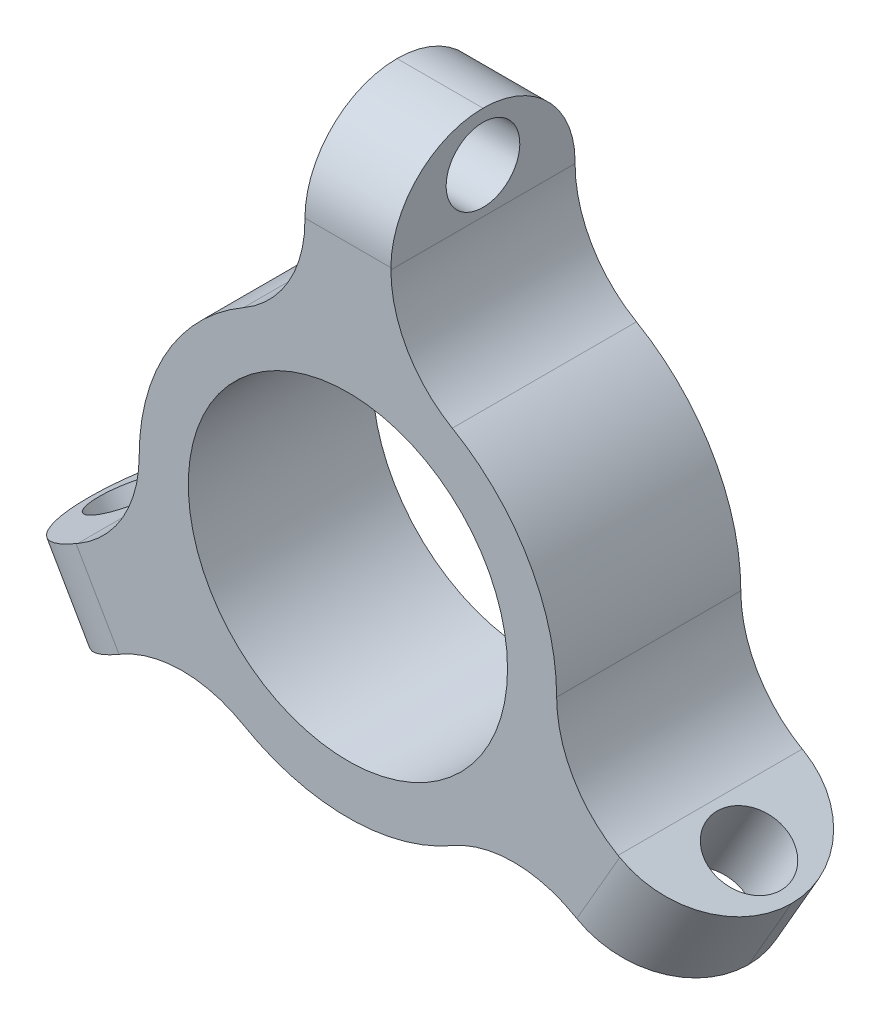
SolidWorks part; units mm, degrees
material "BUTYL"
ref_plane "Plan de face" through (0, 0, 0) normal (0, 0, 1) x (1, 0, 0)
ref_plane "Plan de dessus" through (0, 0, 0) normal (0, 1, 0) x (1, 0, 0)
ref_plane "Plan de droite" through (0, 0, 0) normal (1, 0, 0) x (0, 0, -1)
sketch "Esquisse1" plane through (0, 0, 0) normal (0, 0, 1) x (1, 0, 0)
  line L0 (0, 21.0412) -> (0, 29.5771) construction
  line L1 (-3.5, 23.3827) -> (-3.5, 31.0412)
  line L2 (-3.5, 31.0412) -> (3.5, 31.0412)
  line L3 (3.5, 31.0412) -> (3.5, 23.3827)
  line L4 (25.1325, -18.5517) -> (18.5, -14.7224)
  line L5 (28.6325, -12.4895) -> (25.1325, -18.5517)
  line L6 (22, -8.6603) -> (28.6325, -12.4895)
  line L7 (-28.6325, -12.4895) -> (-22, -8.6603)
  line L8 (-25.1325, -18.5517) -> (-28.6325, -12.4895)
  line L9 (-18.5, -14.7224) -> (-25.1325, -18.5517)
  circle A0 centre (0, 0) radius 13
  arc A1 (-8.5, 14.7224) -> (-17, 0) centre (0, 0) ccw
  arc A2 (17, 0) -> (8.5, 14.7224) centre (0, 0) ccw
  arc A3 (-8.5, -14.7224) -> (8.5, -14.7224) centre (0, 0) ccw
  arc A4 (-8.5, -14.7224) -> (-18.5, -14.7224) centre (-13.5, -23.3827) ccw
  arc A5 (-8.5, 14.7224) -> (-3.5, 23.3827) centre (-13.5, 23.3827) ccw
  arc A6 (3.5, 23.3827) -> (8.5, 14.7224) centre (13.5, 23.3827) ccw
  arc A7 (17, 0) -> (22, -8.6603) centre (27, 0) ccw
  arc A8 (18.5, -14.7224) -> (8.5, -14.7224) centre (13.5, -23.3827) ccw
  arc A9 (-17, 0) -> (-22, -8.6603) centre (-27, 0) cw
  point P21 (0, 0)
  dimension "D1" = 26
  dimension "D2" = 4
  dimension "D7" = 10
  dimension "D8" = 10
  dimension "D3" = 10
  dimension "D4" = 7
  dimension "D5" = 3.5
  dimension "D6" = 3
extrude "Boss.-Extru.1" add sketch "Esquisse1" along normal blind 15
fillet "Congé1" radius 7.5 2 edges at (0, 31.0412, 0) (0, 31.0412, 15)
fillet "Congé2" radius 7.5 2 edges at (26.8825, -15.5206, 0) (26.8825, -15.5206, 15)
fillet "Congé3" radius 7.5 2 edges at (-26.8825, -15.5206, 15) (-26.8825, -15.5206, 0)
sketch "Esquisse2" plane through (-1.75, -3.0311, 0) normal (-0.5, -0.866, 0) x (0.866, -0.5, 0)
  line L0 (23.3827, 0) -> (23.5412, 0) construction
  circle A0 centre (27.0412, 7.5) radius 3
  arc A1 (31.0412, 7.5) -> (23.5412, 15) centre (23.5412, 7.5) ccw construction
  dimension "D1" = 6
  dimension "D2" = 0
  dimension "D3" = 4
  dimension "D4" = 7.5
extrude "Enlèv. mat.-Extru.1" cut sketch "Esquisse2" against normal up to next
pattern_circular "Répétition circulaire1" count 3 over 360 about axis through (0, 0, 15) along (0, 0, -1) of "Enlèv. mat.-Extru.1"
